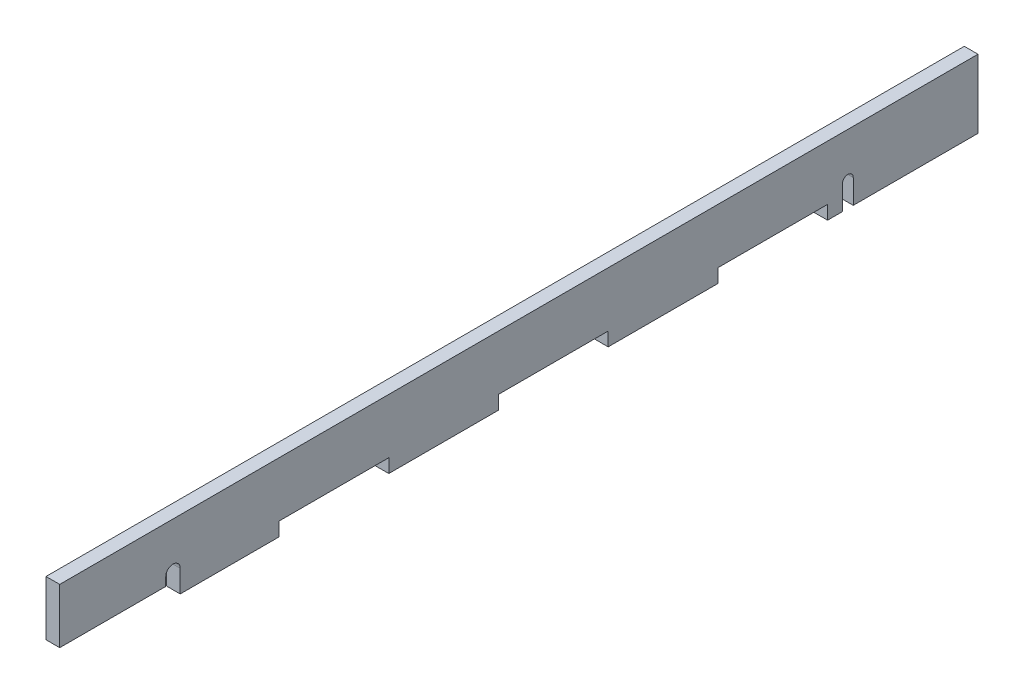
SolidWorks part; units mm, degrees
ref_plane "Front Plane" through (0, 0, 0) normal (0, 0, 1) x (1, 0, 0)
ref_plane "Top Plane" through (0, 0, 0) normal (0, 1, 0) x (1, 0, 0)
ref_plane "Right Plane" through (0, 0, 0) normal (1, 0, 0) x (0, 0, -1)
sketch "Sketch2" plane through (0, 0, 0) normal (1, 0, 0) x (0, 0, -1)
  line L30 (48.3194, 0) -> (99.1194, 0)
  line L31 (-2.4806, 6.35) -> (-2.4806, 31.75)
  line L32 (-2.4806, 31.75) -> (422.7895, 31.75)
  line L33 (422.7895, 0) -> (422.7895, 31.75)
  line L34 (353.1194, 6.35) -> (353.1194, 0) construction
  line L35 (302.3194, 6.35) -> (353.1194, 6.35) construction
  line L36 (302.3194, 6.35) -> (302.3194, 0) construction
  line L37 (251.5194, 6.35) -> (251.5194, 0) construction
  line L38 (200.7194, 6.35) -> (251.5194, 6.35) construction
  line L39 (200.7194, 6.35) -> (200.7194, 0) construction
  line L40 (149.9194, 6.35) -> (149.9194, 0) construction
  line L41 (99.1194, 6.35) -> (149.9194, 6.35) construction
  line L42 (99.1194, 6.35) -> (99.1194, 0) construction
  line L43 (48.3194, 6.35) -> (48.3194, 0) construction
  line L44 (-2.4806, 6.35) -> (48.3194, 6.35) construction
  line L45 (422.7895, 31.75) -> (422.7895, 35.3357) construction
  line L46 (353.1194, 6.35) -> (353.1194, 0)
  line L47 (302.3194, 6.35) -> (353.1194, 6.35)
  line L48 (302.3194, 6.35) -> (302.3194, 0)
  line L49 (251.5194, 6.35) -> (251.5194, 0)
  line L50 (200.7194, 6.35) -> (251.5194, 6.35)
  line L51 (200.7194, 6.35) -> (200.7194, 0)
  line L52 (149.9194, 6.35) -> (149.9194, 0)
  line L53 (99.1194, 6.35) -> (149.9194, 6.35)
  line L54 (99.1194, 6.35) -> (99.1194, 0)
  line L55 (48.3194, 6.35) -> (48.3194, 0)
  line L56 (-2.4806, 6.35) -> (48.3194, 6.35)
  line L57 (353.1194, 0) -> (422.7895, 0)
  line L58 (251.5194, 0) -> (302.3194, 0)
  line L59 (149.9194, 0) -> (200.7194, 0)
extrude "Boss-Extrude1" add sketch "Sketch2" along normal blind 6.35
sketch "Sketch3" plane through (6.35, 0, 0) normal (1, 0, 0) x (0, 0, -1)
  line L0 (353.1194, 6.35) -> (422.7895, 6.35) construction
  line L1 (422.7895, 0) -> (422.7895, 31.75) construction
  line L2 (362.5194, 8.66) -> (362.5194, 6.35) construction
  line L3 (-2.4806, 31.75) -> (-2.4806, 6.35) construction
  line L5 (365.0194, 11.16) -> (365.0194, -0.0346)
  line L6 (360.0194, 11.16) -> (360.0194, -0.0346)
  line L7 (365.0194, -0.0346) -> (360.0194, -0.0346)
  arc A0 (365.0194, 11.16) -> (360.0194, 11.16) centre (362.5194, 11.16) ccw
  dimension "D1" = 5
  dimension "D2" = 2.31
  dimension "D3" = 365
extrude "Cut-Extrude1" cut sketch "Sketch3" against normal up to next
sketch "Sketch4" plane through (6.35, 0, 0) normal (1, 0, 0) x (0, 0, -1)
  line L1 (53.3194, 10.31) -> (53.3194, 0)
  line L2 (48.3194, 6.35) -> (48.3194, 0)
  line L3 (53.3194, 0) -> (48.3194, 0)
  line L4 (48.3194, 0) -> (99.1194, 0) construction
  line L6 (-2.4806, 6.35) -> (48.3194, 6.35) construction
  line L7 (48.3194, 6.35) -> (48.3194, 0) construction
  line L9 (48.3194, 6.35) -> (46.6194, 6.35)
  line L10 (46.6194, 10.31) -> (46.6194, 6.35)
  arc A1 (53.3194, 10.31) -> (46.6194, 10.31) centre (49.9694, 10.31) ccw
  point P1 (49.9694, 13.66)
  dimension "D1" = 7.31
  dimension "D2" = 1.7
  dimension "D4" = 5
extrude "Cut-Extrude2" cut sketch "Sketch4" against normal through all
